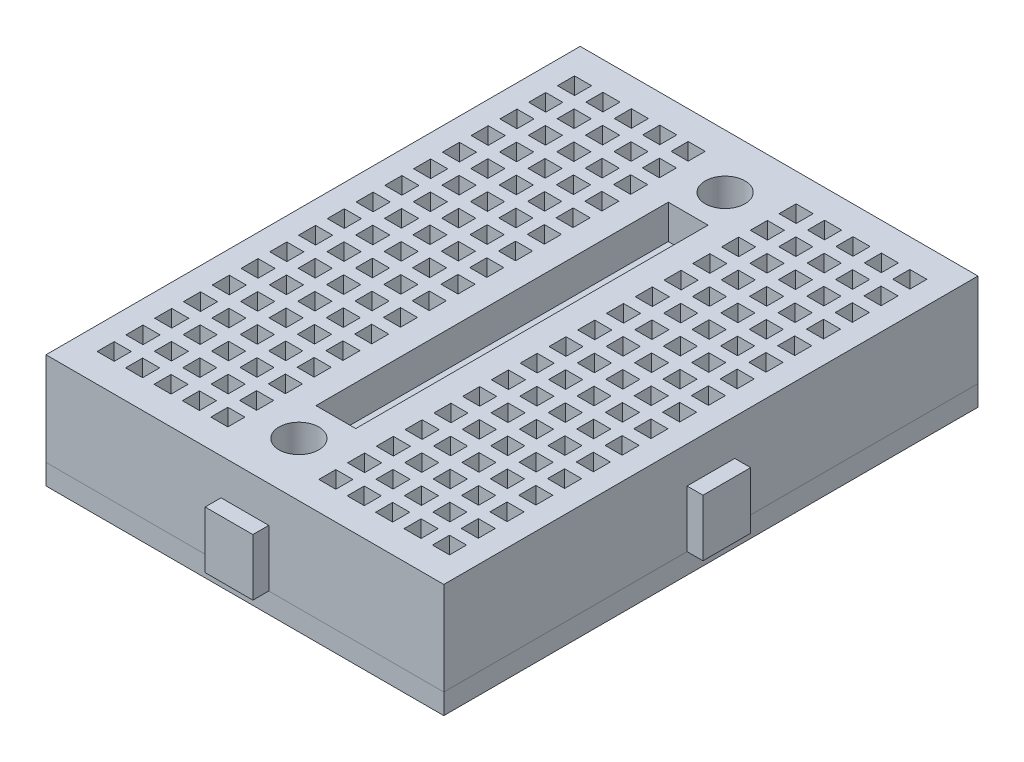
SolidWorks part; units mm, degrees
ref_plane "Front Plane" through (0, 0, 0) normal (0, 0, 1) x (1, 0, 0)
ref_plane "Top Plane" through (0, 0, 0) normal (0, 1, 0) x (1, 0, 0)
ref_plane "Right Plane" through (0, 0, 0) normal (1, 0, 0) x (0, 0, -1)
sketch "Sketch2" plane through (0, 0, 0) normal (0, 1, 0) x (1, 0, 0)
  line L1 (0, 23.5) -> (-17.5, 23.5)
  line L2 (0, 23.5) -> (0, -23.5)
  line L3 (0, -23.5) -> (-17.5, -23.5)
  line L4 (-17.5, 23.5) -> (-17.5, -23.5)
  line L5 (0, 23.5) -> (-17.5, -23.5) construction
  line L6 (0, -23.5) -> (-17.5, 23.5) construction
  point P0 (0, 0)
  point P6 (0, 0)
  point P7 (0, 0)
  dimension "D1" = 17.5
  dimension "D2" = 47
extrude "Boss-Extrude1" add sketch "Sketch2" along normal blind 5.2
sketch "Sketch3" plane through (0, 5.2, 0) normal (0, 1, 0) x (1, 0, 0)
  line L0 (0, -23.5) -> (0, 23.5) construction
  line L5 (1.75, -15.5) -> (-1.75, -15.5)
  line L6 (1.75, -15.5) -> (1.75, 15.5)
  line L7 (0, 23.5) -> (-17.5, 23.5) construction
  line L8 (-17.5, -23.5) -> (0, -23.5) construction
  line L9 (1.75, 15.5) -> (-1.75, 15.5)
  line L10 (-1.75, -15.5) -> (-1.75, 15.5)
  line L12 (-13, 21) -> (-13, 19.5)
  line L13 (-15.5, 21) -> (-14, 21)
  line L14 (-15.5, 21) -> (-15.5, 19.5)
  line L15 (-15.5, 19.5) -> (-14, 19.5)
  line L16 (-14, 21) -> (-14, 19.5)
  line L17 (-13, 21) -> (-11.5, 21)
  line L18 (-11.5, 21) -> (-11.5, 19.5)
  line L19 (-13, 19.5) -> (-11.5, 19.5)
  line L20 (-10.5, 21) -> (-10.5, 19.5)
  line L21 (-10.5, 21) -> (-9, 21)
  line L22 (-9, 21) -> (-9, 19.5)
  line L23 (-10.5, 19.5) -> (-9, 19.5)
  line L24 (-8, 21) -> (-8, 19.5)
  line L25 (-8, 21) -> (-6.5, 21)
  line L26 (-6.5, 21) -> (-6.5, 19.5)
  line L27 (-8, 19.5) -> (-6.5, 19.5)
  line L28 (-5.5, 21) -> (-5.5, 19.5)
  line L29 (-5.5, 21) -> (-4, 21)
  line L30 (-4, 21) -> (-4, 19.5)
  line L31 (-5.5, 19.5) -> (-4, 19.5)
  line L32 (-13, 18.4688) -> (-13, 16.9687)
  line L33 (-13, 18.4688) -> (-11.5, 18.4688)
  line L34 (-11.5, 18.4688) -> (-11.5, 16.9687)
  line L35 (-13, 16.9687) -> (-11.5, 16.9687)
  line L36 (-10.5, 18.4688) -> (-10.5, 16.9687)
  line L37 (-10.5, 18.4688) -> (-9, 18.4688)
  line L38 (-9, 18.4688) -> (-9, 16.9687)
  line L39 (-10.5, 16.9687) -> (-9, 16.9687)
  line L40 (-8, 18.4688) -> (-8, 16.9687)
  line L41 (-8, 18.4688) -> (-6.5, 18.4688)
  line L42 (-6.5, 18.4688) -> (-6.5, 16.9687)
  line L43 (-8, 16.9687) -> (-6.5, 16.9687)
  line L44 (-5.5, 18.4688) -> (-5.5, 16.9687)
  line L45 (-5.5, 18.4688) -> (-4, 18.4688)
  line L46 (-4, 18.4688) -> (-4, 16.9687)
  line L47 (-5.5, 16.9687) -> (-4, 16.9687)
  line L48 (-13, 15.9375) -> (-13, 14.4375)
  line L49 (-13, 15.9375) -> (-11.5, 15.9375)
  line L50 (-11.5, 15.9375) -> (-11.5, 14.4375)
  line L51 (-13, 14.4375) -> (-11.5, 14.4375)
  line L52 (-10.5, 15.9375) -> (-10.5, 14.4375)
  line L53 (-10.5, 15.9375) -> (-9, 15.9375)
  line L54 (-9, 15.9375) -> (-9, 14.4375)
  line L55 (-10.5, 14.4375) -> (-9, 14.4375)
  line L56 (-8, 15.9375) -> (-8, 14.4375)
  line L57 (-8, 15.9375) -> (-6.5, 15.9375)
  line L58 (-6.5, 15.9375) -> (-6.5, 14.4375)
  line L59 (-8, 14.4375) -> (-6.5, 14.4375)
  line L60 (-5.5, 15.9375) -> (-5.5, 14.4375)
  line L61 (-5.5, 15.9375) -> (-4, 15.9375)
  line L62 (-4, 15.9375) -> (-4, 14.4375)
  line L63 (-5.5, 14.4375) -> (-4, 14.4375)
  line L64 (-13, 13.4063) -> (-13, 11.9062)
  line L65 (-13, 13.4063) -> (-11.5, 13.4063)
  line L66 (-11.5, 13.4063) -> (-11.5, 11.9062)
  line L67 (-13, 11.9062) -> (-11.5, 11.9062)
  line L68 (-10.5, 13.4063) -> (-10.5, 11.9062)
  line L69 (-10.5, 13.4063) -> (-9, 13.4063)
  line L70 (-9, 13.4063) -> (-9, 11.9062)
  line L71 (-10.5, 11.9062) -> (-9, 11.9062)
  line L72 (-8, 13.4063) -> (-8, 11.9062)
  line L73 (-8, 13.4063) -> (-6.5, 13.4063)
  line L74 (-6.5, 13.4063) -> (-6.5, 11.9062)
  line L75 (-8, 11.9062) -> (-6.5, 11.9062)
  line L76 (-5.5, 13.4063) -> (-5.5, 11.9062)
  line L77 (-5.5, 13.4063) -> (-4, 13.4063)
  line L78 (-4, 13.4063) -> (-4, 11.9062)
  line L79 (-5.5, 11.9062) -> (-4, 11.9062)
  line L80 (-13, 10.875) -> (-13, 9.375)
  line L81 (-13, 10.875) -> (-11.5, 10.875)
  line L82 (-11.5, 10.875) -> (-11.5, 9.375)
  line L83 (-13, 9.375) -> (-11.5, 9.375)
  line L84 (-10.5, 10.875) -> (-10.5, 9.375)
  line L85 (-10.5, 10.875) -> (-9, 10.875)
  line L86 (-9, 10.875) -> (-9, 9.375)
  line L87 (-10.5, 9.375) -> (-9, 9.375)
  line L88 (-8, 10.875) -> (-8, 9.375)
  line L89 (-8, 10.875) -> (-6.5, 10.875)
  line L90 (-6.5, 10.875) -> (-6.5, 9.375)
  line L91 (-8, 9.375) -> (-6.5, 9.375)
  line L92 (-5.5, 10.875) -> (-5.5, 9.375)
  line L93 (-5.5, 10.875) -> (-4, 10.875)
  line L94 (-4, 10.875) -> (-4, 9.375)
  line L95 (-5.5, 9.375) -> (-4, 9.375)
  line L96 (-13, 8.3438) -> (-13, 6.8438)
  line L97 (-13, 8.3438) -> (-11.5, 8.3438)
  line L98 (-11.5, 8.3438) -> (-11.5, 6.8438)
  line L99 (-13, 6.8438) -> (-11.5, 6.8438)
  line L100 (-10.5, 8.3438) -> (-10.5, 6.8438)
  line L101 (-10.5, 8.3438) -> (-9, 8.3438)
  line L102 (-9, 8.3438) -> (-9, 6.8438)
  line L103 (-10.5, 6.8438) -> (-9, 6.8438)
  line L104 (-8, 8.3438) -> (-8, 6.8438)
  line L105 (-8, 8.3438) -> (-6.5, 8.3438)
  line L106 (-6.5, 8.3438) -> (-6.5, 6.8438)
  line L107 (-8, 6.8438) -> (-6.5, 6.8438)
  line L108 (-5.5, 8.3438) -> (-5.5, 6.8438)
  line L109 (-5.5, 8.3438) -> (-4, 8.3438)
  line L110 (-4, 8.3438) -> (-4, 6.8438)
  line L111 (-5.5, 6.8438) -> (-4, 6.8438)
  line L112 (-13, 5.8125) -> (-13, 4.3125)
  line L113 (-13, 5.8125) -> (-11.5, 5.8125)
  line L114 (-11.5, 5.8125) -> (-11.5, 4.3125)
  line L115 (-13, 4.3125) -> (-11.5, 4.3125)
  line L116 (-10.5, 5.8125) -> (-10.5, 4.3125)
  line L117 (-10.5, 5.8125) -> (-9, 5.8125)
  line L118 (-9, 5.8125) -> (-9, 4.3125)
  line L119 (-10.5, 4.3125) -> (-9, 4.3125)
  line L120 (-8, 5.8125) -> (-8, 4.3125)
  line L121 (-8, 5.8125) -> (-6.5, 5.8125)
  line L122 (-6.5, 5.8125) -> (-6.5, 4.3125)
  line L123 (-8, 4.3125) -> (-6.5, 4.3125)
  line L124 (-5.5, 5.8125) -> (-5.5, 4.3125)
  line L125 (-5.5, 5.8125) -> (-4, 5.8125)
  line L126 (-4, 5.8125) -> (-4, 4.3125)
  line L127 (-5.5, 4.3125) -> (-4, 4.3125)
  line L128 (-13, 3.2813) -> (-13, 1.7813)
  line L129 (-13, 3.2813) -> (-11.5, 3.2813)
  line L130 (-11.5, 3.2813) -> (-11.5, 1.7813)
  line L131 (-13, 1.7813) -> (-11.5, 1.7813)
  line L132 (-10.5, 3.2813) -> (-10.5, 1.7813)
  line L133 (-10.5, 3.2813) -> (-9, 3.2813)
  line L134 (-9, 3.2813) -> (-9, 1.7813)
  line L135 (-10.5, 1.7813) -> (-9, 1.7813)
  line L136 (-8, 3.2813) -> (-8, 1.7813)
  line L137 (-8, 3.2813) -> (-6.5, 3.2813)
  line L138 (-6.5, 3.2813) -> (-6.5, 1.7813)
  line L139 (-8, 1.7813) -> (-6.5, 1.7813)
  line L140 (-5.5, 3.2813) -> (-5.5, 1.7813)
  line L141 (-5.5, 3.2813) -> (-4, 3.2813)
  line L142 (-4, 3.2813) -> (-4, 1.7813)
  line L143 (-5.5, 1.7813) -> (-4, 1.7813)
  line L144 (-13, 0.75) -> (-13, -0.75)
  line L145 (-13, 0.75) -> (-11.5, 0.75)
  line L146 (-11.5, 0.75) -> (-11.5, -0.75)
  line L147 (-13, -0.75) -> (-11.5, -0.75)
  line L148 (-10.5, 0.75) -> (-10.5, -0.75)
  line L149 (-10.5, 0.75) -> (-9, 0.75)
  line L150 (-9, 0.75) -> (-9, -0.75)
  line L151 (-10.5, -0.75) -> (-9, -0.75)
  line L152 (-8, 0.75) -> (-8, -0.75)
  line L153 (-8, 0.75) -> (-6.5, 0.75)
  line L154 (-6.5, 0.75) -> (-6.5, -0.75)
  line L155 (-8, -0.75) -> (-6.5, -0.75)
  line L156 (-5.5, 0.75) -> (-5.5, -0.75)
  line L157 (-5.5, 0.75) -> (-4, 0.75)
  line L158 (-4, 0.75) -> (-4, -0.75)
  line L159 (-5.5, -0.75) -> (-4, -0.75)
  line L160 (-13, -1.7812) -> (-13, -3.2812)
  line L161 (-13, -1.7812) -> (-11.5, -1.7812)
  line L162 (-11.5, -1.7812) -> (-11.5, -3.2812)
  line L163 (-13, -3.2812) -> (-11.5, -3.2812)
  line L164 (-10.5, -1.7812) -> (-10.5, -3.2812)
  line L165 (-10.5, -1.7812) -> (-9, -1.7812)
  line L166 (-9, -1.7812) -> (-9, -3.2812)
  line L167 (-10.5, -3.2812) -> (-9, -3.2812)
  line L168 (-8, -1.7812) -> (-8, -3.2812)
  line L169 (-8, -1.7812) -> (-6.5, -1.7812)
  line L170 (-6.5, -1.7812) -> (-6.5, -3.2812)
  line L171 (-8, -3.2812) -> (-6.5, -3.2812)
  line L172 (-5.5, -1.7812) -> (-5.5, -3.2812)
  line L173 (-5.5, -1.7812) -> (-4, -1.7812)
  line L174 (-4, -1.7812) -> (-4, -3.2812)
  line L175 (-5.5, -3.2812) -> (-4, -3.2812)
  line L176 (-13, -4.3125) -> (-13, -5.8125)
  line L177 (-13, -4.3125) -> (-11.5, -4.3125)
  line L178 (-11.5, -4.3125) -> (-11.5, -5.8125)
  line L179 (-13, -5.8125) -> (-11.5, -5.8125)
  line L180 (-10.5, -4.3125) -> (-10.5, -5.8125)
  line L181 (-10.5, -4.3125) -> (-9, -4.3125)
  line L182 (-9, -4.3125) -> (-9, -5.8125)
  line L183 (-10.5, -5.8125) -> (-9, -5.8125)
  line L184 (-8, -4.3125) -> (-8, -5.8125)
  line L185 (-8, -4.3125) -> (-6.5, -4.3125)
  line L186 (-6.5, -4.3125) -> (-6.5, -5.8125)
  line L187 (-8, -5.8125) -> (-6.5, -5.8125)
  line L188 (-5.5, -4.3125) -> (-5.5, -5.8125)
  line L189 (-5.5, -4.3125) -> (-4, -4.3125)
  line L190 (-4, -4.3125) -> (-4, -5.8125)
  line L191 (-5.5, -5.8125) -> (-4, -5.8125)
  line L192 (-13, -6.8437) -> (-13, -8.3437)
  line L193 (-13, -6.8437) -> (-11.5, -6.8437)
  line L194 (-11.5, -6.8437) -> (-11.5, -8.3437)
  line L195 (-13, -8.3437) -> (-11.5, -8.3437)
  line L196 (-10.5, -6.8437) -> (-10.5, -8.3437)
  line L197 (-10.5, -6.8437) -> (-9, -6.8437)
  line L198 (-9, -6.8437) -> (-9, -8.3437)
  line L199 (-10.5, -8.3437) -> (-9, -8.3437)
  line L200 (-8, -6.8437) -> (-8, -8.3437)
  line L201 (-8, -6.8437) -> (-6.5, -6.8437)
  line L202 (-6.5, -6.8437) -> (-6.5, -8.3437)
  line L203 (-8, -8.3437) -> (-6.5, -8.3437)
  line L204 (-5.5, -6.8437) -> (-5.5, -8.3437)
  line L205 (-5.5, -6.8437) -> (-4, -6.8437)
  line L206 (-4, -6.8437) -> (-4, -8.3437)
  line L207 (-5.5, -8.3437) -> (-4, -8.3437)
  line L208 (-13, -9.375) -> (-13, -10.875)
  line L209 (-13, -9.375) -> (-11.5, -9.375)
  line L210 (-11.5, -9.375) -> (-11.5, -10.875)
  line L211 (-13, -10.875) -> (-11.5, -10.875)
  line L212 (-10.5, -9.375) -> (-10.5, -10.875)
  line L213 (-10.5, -9.375) -> (-9, -9.375)
  line L214 (-9, -9.375) -> (-9, -10.875)
  line L215 (-10.5, -10.875) -> (-9, -10.875)
  line L216 (-8, -9.375) -> (-8, -10.875)
  line L217 (-8, -9.375) -> (-6.5, -9.375)
  line L218 (-6.5, -9.375) -> (-6.5, -10.875)
  line L219 (-8, -10.875) -> (-6.5, -10.875)
  line L220 (-5.5, -9.375) -> (-5.5, -10.875)
  line L221 (-5.5, -9.375) -> (-4, -9.375)
  line L222 (-4, -9.375) -> (-4, -10.875)
  line L223 (-5.5, -10.875) -> (-4, -10.875)
  line L224 (-13, -11.9062) -> (-13, -13.4062)
  line L225 (-13, -11.9062) -> (-11.5, -11.9062)
  line L226 (-11.5, -11.9062) -> (-11.5, -13.4062)
  line L227 (-13, -13.4062) -> (-11.5, -13.4062)
  line L228 (-10.5, -11.9062) -> (-10.5, -13.4062)
  line L229 (-10.5, -11.9062) -> (-9, -11.9062)
  line L230 (-9, -11.9062) -> (-9, -13.4062)
  line L231 (-10.5, -13.4062) -> (-9, -13.4062)
  line L232 (-8, -11.9062) -> (-8, -13.4062)
  line L233 (-8, -11.9062) -> (-6.5, -11.9062)
  line L234 (-6.5, -11.9062) -> (-6.5, -13.4062)
  line L235 (-8, -13.4062) -> (-6.5, -13.4062)
  line L236 (-5.5, -11.9062) -> (-5.5, -13.4062)
  line L237 (-5.5, -11.9062) -> (-4, -11.9062)
  line L238 (-4, -11.9062) -> (-4, -13.4062)
  line L239 (-5.5, -13.4062) -> (-4, -13.4062)
  line L240 (-13, -14.4375) -> (-13, -15.9375)
  line L241 (-13, -14.4375) -> (-11.5, -14.4375)
  line L242 (-11.5, -14.4375) -> (-11.5, -15.9375)
  line L243 (-13, -15.9375) -> (-11.5, -15.9375)
  line L244 (-10.5, -14.4375) -> (-10.5, -15.9375)
  line L245 (-10.5, -14.4375) -> (-9, -14.4375)
  line L246 (-9, -14.4375) -> (-9, -15.9375)
  line L247 (-10.5, -15.9375) -> (-9, -15.9375)
  line L248 (-8, -14.4375) -> (-8, -15.9375)
  line L249 (-8, -14.4375) -> (-6.5, -14.4375)
  line L250 (-6.5, -14.4375) -> (-6.5, -15.9375)
  line L251 (-8, -15.9375) -> (-6.5, -15.9375)
  line L252 (-5.5, -14.4375) -> (-5.5, -15.9375)
  line L253 (-5.5, -14.4375) -> (-4, -14.4375)
  line L254 (-4, -14.4375) -> (-4, -15.9375)
  line L255 (-5.5, -15.9375) -> (-4, -15.9375)
  line L256 (-13, -16.9687) -> (-13, -18.4687)
  line L257 (-13, -16.9687) -> (-11.5, -16.9687)
  line L258 (-11.5, -16.9687) -> (-11.5, -18.4687)
  line L259 (-13, -18.4687) -> (-11.5, -18.4687)
  line L260 (-10.5, -16.9687) -> (-10.5, -18.4687)
  line L261 (-10.5, -16.9687) -> (-9, -16.9687)
  line L262 (-9, -16.9687) -> (-9, -18.4687)
  line L263 (-10.5, -18.4687) -> (-9, -18.4687)
  line L264 (-8, -16.9687) -> (-8, -18.4687)
  line L265 (-8, -16.9687) -> (-6.5, -16.9687)
  line L266 (-6.5, -16.9687) -> (-6.5, -18.4687)
  line L267 (-8, -18.4687) -> (-6.5, -18.4687)
  line L268 (-5.5, -16.9687) -> (-5.5, -18.4687)
  line L269 (-5.5, -16.9687) -> (-4, -16.9687)
  line L270 (-4, -16.9687) -> (-4, -18.4687)
  line L271 (-5.5, -18.4687) -> (-4, -18.4687)
  line L272 (-13, -19.5) -> (-13, -21)
  line L273 (-13, -19.5) -> (-11.5, -19.5)
  line L274 (-11.5, -19.5) -> (-11.5, -21)
  line L275 (-13, -21) -> (-11.5, -21)
  line L276 (-10.5, -19.5) -> (-10.5, -21)
  line L277 (-10.5, -19.5) -> (-9, -19.5)
  line L278 (-9, -19.5) -> (-9, -21)
  line L279 (-10.5, -21) -> (-9, -21)
  line L280 (-8, -19.5) -> (-8, -21)
  line L281 (-8, -19.5) -> (-6.5, -19.5)
  line L282 (-6.5, -19.5) -> (-6.5, -21)
  line L283 (-8, -21) -> (-6.5, -21)
  line L284 (-5.5, -19.5) -> (-5.5, -21)
  line L285 (-5.5, -19.5) -> (-4, -19.5)
  line L286 (-4, -19.5) -> (-4, -21)
  line L287 (-5.5, -21) -> (-4, -21)
  line L288 (-15.5, 18.4688) -> (-15.5, 16.9687)
  line L289 (-15.5, 18.4688) -> (-14, 18.4688)
  line L290 (-14, 18.4688) -> (-14, 16.9687)
  line L291 (-15.5, 16.9687) -> (-14, 16.9687)
  line L292 (-15.5, 15.9375) -> (-15.5, 14.4375)
  line L293 (-15.5, 15.9375) -> (-14, 15.9375)
  line L294 (-14, 15.9375) -> (-14, 14.4375)
  line L295 (-15.5, 14.4375) -> (-14, 14.4375)
  line L296 (-15.5, 13.4063) -> (-15.5, 11.9062)
  line L297 (-15.5, 13.4063) -> (-14, 13.4063)
  line L298 (-14, 13.4063) -> (-14, 11.9062)
  line L299 (-15.5, 11.9062) -> (-14, 11.9062)
  line L300 (-15.5, 10.875) -> (-15.5, 9.375)
  line L301 (-15.5, 10.875) -> (-14, 10.875)
  line L302 (-14, 10.875) -> (-14, 9.375)
  line L303 (-15.5, 9.375) -> (-14, 9.375)
  line L304 (-15.5, 8.3438) -> (-15.5, 6.8438)
  line L305 (-15.5, 8.3438) -> (-14, 8.3438)
  line L306 (-14, 8.3438) -> (-14, 6.8438)
  line L307 (-15.5, 6.8438) -> (-14, 6.8438)
  line L308 (-15.5, 5.8125) -> (-15.5, 4.3125)
  line L309 (-15.5, 5.8125) -> (-14, 5.8125)
  line L310 (-14, 5.8125) -> (-14, 4.3125)
  line L311 (-15.5, 4.3125) -> (-14, 4.3125)
  line L312 (-15.5, 3.2813) -> (-15.5, 1.7813)
  line L313 (-15.5, 3.2813) -> (-14, 3.2813)
  line L314 (-14, 3.2813) -> (-14, 1.7813)
  line L315 (-15.5, 1.7813) -> (-14, 1.7813)
  line L316 (-15.5, 0.75) -> (-15.5, -0.75)
  line L317 (-15.5, 0.75) -> (-14, 0.75)
  line L318 (-14, 0.75) -> (-14, -0.75)
  line L319 (-15.5, -0.75) -> (-14, -0.75)
  line L320 (-15.5, -1.7812) -> (-15.5, -3.2812)
  line L321 (-15.5, -1.7812) -> (-14, -1.7812)
  line L322 (-14, -1.7812) -> (-14, -3.2812)
  line L323 (-15.5, -3.2812) -> (-14, -3.2812)
  line L324 (-15.5, -4.3125) -> (-15.5, -5.8125)
  line L325 (-15.5, -4.3125) -> (-14, -4.3125)
  line L326 (-14, -4.3125) -> (-14, -5.8125)
  line L327 (-15.5, -5.8125) -> (-14, -5.8125)
  line L328 (-15.5, -6.8437) -> (-15.5, -8.3437)
  line L329 (-15.5, -6.8437) -> (-14, -6.8437)
  line L330 (-14, -6.8437) -> (-14, -8.3437)
  line L331 (-15.5, -8.3437) -> (-14, -8.3437)
  line L332 (-15.5, -9.375) -> (-15.5, -10.875)
  line L333 (-15.5, -9.375) -> (-14, -9.375)
  line L334 (-14, -9.375) -> (-14, -10.875)
  line L335 (-15.5, -10.875) -> (-14, -10.875)
  line L336 (-15.5, -11.9062) -> (-15.5, -13.4062)
  line L337 (-15.5, -11.9062) -> (-14, -11.9062)
  line L338 (-14, -11.9062) -> (-14, -13.4062)
  line L339 (-15.5, -13.4062) -> (-14, -13.4062)
  line L340 (-15.5, -14.4375) -> (-15.5, -15.9375)
  line L341 (-15.5, -14.4375) -> (-14, -14.4375)
  line L342 (-14, -14.4375) -> (-14, -15.9375)
  line L343 (-15.5, -15.9375) -> (-14, -15.9375)
  line L344 (-15.5, -16.9687) -> (-15.5, -18.4687)
  line L345 (-15.5, -16.9687) -> (-14, -16.9687)
  line L346 (-14, -16.9687) -> (-14, -18.4687)
  line L347 (-15.5, -18.4687) -> (-14, -18.4687)
  line L348 (-15.5, -19.5) -> (-15.5, -21)
  line L349 (-15.5, -19.5) -> (-14, -19.5)
  line L350 (-14, -19.5) -> (-14, -21)
  line L351 (-15.5, -21) -> (-14, -21)
  line L352 (-17.5, 23.5) -> (-17.5, -23.5) construction
  line L353 (-9.75, 21) -> (-9.75, 23.5) construction
  line L354 (-9.75, -21) -> (-9.75, -23.5) construction
  line L355 (1.75, -15.5) -> (-1.75, 15.5) construction
  line L356 (1.75, 15.5) -> (-1.75, -15.5) construction
  line L357 (0, 20.5) -> (0, 23.5) construction
  line L358 (0, 0) -> (-17.5, 0) construction
  circle A4 centre (0, 18.75) radius 1.75
  circle A5 centre (0, -18.75) radius 1.75
  point P0 (0, 0)
  point P1 (0, 0)
  point P36 (-4, 0)
  line M352 (-17.5, 23.5) -> (-17.5, -23.5)
  line M353 (-17.5, -23.5) -> (0, -23.5)
  line M354 (0, -23.5) -> (0, 23.5)
  line M355 (0, 23.5) -> (-17.5, 23.5)
  dimension "D3" = 3
  dimension "D4" = 31
  dimension "D2" = 3.5
  dimension "D5" = 3.5
  dimension "D6" = 1.5
  dimension "D9" = 11.5
  dimension "D10" = 42
  dimension "D11" = 2
  dimension "D7" = 5
  dimension "D8" = 17
extrude "Boss-Extrude2" add sketch "Sketch3" along normal blind 3 contours A4 L5 L10 L9 L351 L348 L349 L350 L347 L344 L345 L346 L343 L340 L341 L342 L339 L336 L337 L338 L335 L332 L333 L334 L331 L328 L329 L330 L327 L324 L325 L326 L323 L320 L321 L322 M354 M355 M352 M353 region at (-0.5015, 5.2, 16.25)
mirror "Mirror1" about plane through (0, 5.2, -23.5) normal (-1, 0, 0) of "Boss-Extrude2", "Boss-Extrude1"
sketch "Sketch4" plane through (0, 5.2, 0) normal (0, 1, 0) x (1, 0, 0)
  circle A0 centre (0, 18.75) radius 1
  circle A1 centre (0, -18.75) radius 1
  dimension "D1" = 2
extrude "Cut-Extrude1" cut sketch "Sketch4" against normal through all
sketch "Sketch7" plane through (0, 0, 23.5) normal (0, 0, 1) x (1, 0, 0)
  line L0 (-17.5, 0) -> (17.5, 0) construction
  line L1 (2.1, 5) -> (-2.1, 5)
  line L2 (2.1, 5) -> (2.1, 0)
  line L3 (2.1, 0) -> (-2.1, 0)
  line L4 (-2.1, 5) -> (-2.1, 0)
  line L5 (2.1, 5) -> (-2.1, 0) construction
  line L6 (2.1, 0) -> (-2.1, 5) construction
  point P0 (0, 2.5)
  point P7 (0, 0)
  dimension "D1" = 4.2
  dimension "D2" = 5
extrude "Boss-Extrude4" add sketch "Sketch7" along normal blind 1.4
sketch "Sketch8" plane through (0, 0, -23.5) normal (0, 0, -1) x (-1, 0, 0)
  line L0 (-2.1, 5) -> (-2.1, 0) construction
  line L1 (-2.1, 0) -> (2.1, 0) construction
  line L2 (2.1, 5) -> (2.1, 0) construction
  line L3 (-2.1, 5) -> (2.1, 5) construction
  line L4 (-2.1, 5) -> (-2.1, 0)
  line L5 (-2.1, 0) -> (2.1, 0)
  line L6 (2.1, 5) -> (2.1, 0)
  line L7 (-2.1, 5) -> (2.1, 5)
extrude "Cut-Extrude2" cut sketch "Sketch8" against normal blind 1.7
sketch "Sketch9" plane through (17.5, 0, 0) normal (1, 0, 0) x (0, 0, -1)
  line L0 (23.5, 0) -> (-23.5, 0) construction
  line L1 (2.1, 5) -> (-2.1, 5)
  line L2 (2.1, 5) -> (2.1, 0)
  line L3 (2.1, 0) -> (-2.1, 0)
  line L4 (-2.1, 5) -> (-2.1, 0)
  line L5 (2.1, 5) -> (-2.1, 0) construction
  line L6 (2.1, 0) -> (-2.1, 5) construction
  point P0 (0, 2.5)
  point P7 (-0.6439, 3.9077)
  point P8 (0, 0)
  dimension "D1" = 4.2
  dimension "D2" = 5
extrude "Boss-Extrude5" add sketch "Sketch9" along normal blind 1.4
sketch "Sketch10" plane through (-17.5, 0, 0) normal (-1, 0, 0) x (0, 0, 1)
  line L0 (-2.1, 0) -> (2.1, 0) construction
  line L1 (2.1, 5) -> (2.1, 0) construction
  line L2 (-2.1, 5) -> (-2.1, 0) construction
  line L3 (-2.1, 5) -> (2.1, 5) construction
  line L4 (-2.1, 0) -> (2.1, 0)
  line L5 (2.1, 5) -> (2.1, 0)
  line L6 (-2.1, 5) -> (-2.1, 0)
  line L7 (-2.1, 5) -> (2.1, 5)
extrude "Cut-Extrude3" cut sketch "Sketch10" against normal blind 1.7
sketch "Sketch6" plane through (0, 0, 0) normal (0, -1, 0) x (1, 0, 0)
  line L1 (17.5, -23.5) -> (-17.5, -23.5)
  line L2 (17.5, -23.5) -> (17.5, 23.5)
  line L3 (17.5, 23.5) -> (-17.5, 23.5)
  line L4 (-17.5, -23.5) -> (-17.5, 23.5)
  line L5 (17.5, -23.5) -> (-17.5, 23.5) construction
  line L6 (17.5, 23.5) -> (-17.5, -23.5) construction
  point P0 (0, 0)
extrude "Adhesive" add sketch "Sketch6" along normal blind 1.8 separate body
